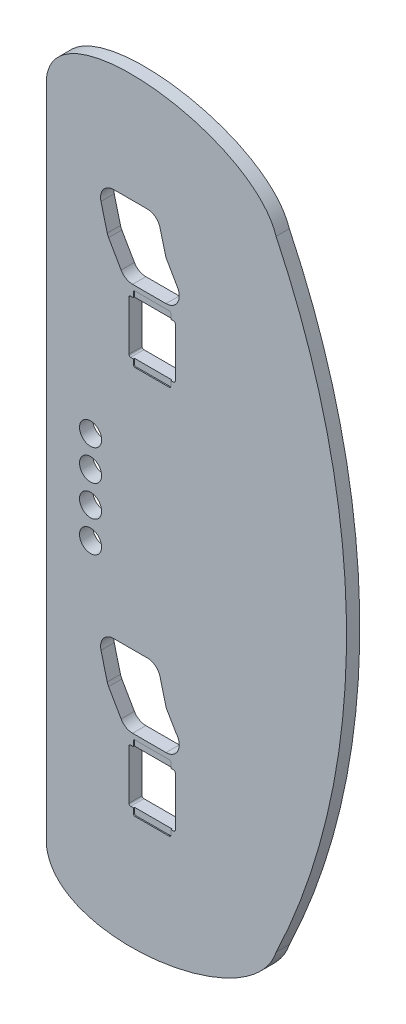
SolidWorks part; units mm, degrees
material "Pine"
ref_plane "Front Plane" through (0, 0, 0) normal (0, 0, 1) x (1, 0, 0)
ref_plane "Top Plane" through (0, 0, 0) normal (0, 1, 0) x (1, 0, 0)
ref_plane "Right Plane" through (0, 0, 0) normal (1, 0, 0) x (0, 0, -1)
sketch "Sketch1" plane through (0, 0, 0) normal (0, 1, 0) x (1, 0, 0)
  line L0 (-92.9216, 89.0184) -> (669.0784, 89.0184)
  line L1 (669.0784, 89.0184) -> (669.0784, 419.2184)
  line L2 (-92.9216, 89.0184) -> (-92.9216, 419.2184)
  line L5 (110.2784, 495.4184) -> (465.8784, 495.4184)
  line L8 (110.2784, 495.4184) -> (-92.9216, 419.2184)
  line L9 (465.8784, 495.4184) -> (669.0784, 419.2184)
  line L10 (-92.9216, 495.4184) -> (669.0784, 495.4184) construction
sketch "Sketch2" plane through (0, 0, 0) normal (0, 0, 1) x (1, 0, 0)
  line L95 (1361.0966, 1819.7347) -> (1361.0966, 996.3635)
  arc A0 (1691.2966, 1027.0491) -> (1691.2966, 1789.0491) centre (733.0004, 1408.0491) ccw
  spline S0 degree 3 poles (1691.2966, 1027.0491) (1656.7077, 922.0591) (1371.3251, 886.2968) (1361.0966, 996.3635) knots 0 0 0 0 7.629784 7.629784 7.629784 7.629784
  spline S1 degree 3 poles (1691.2966, 1789.0491) (1656.7629, 1894.0573) (1371.3251, 1929.8013) (1361.0966, 1819.7347) knots 0 0 0 0 7.638295 7.638295 7.638295 7.638295
sketch "Sketch4" plane through (0, 0, 0) normal (0, 0, 1) x (1, 0, 0)
  line L0 (1439.599, 1277.0692) -> (1448.5991, 1242.0693)
  line L1 (1450.5414, 1237.3053) -> (1468.5414, 1206.0553)
  line L2 (1540.0357, 1097.2035) -> (1540.0357, 1104.1885)
  line L3 (1486.0607, 1185.151) -> (1486.0607, 1006.8697) construction
  line L4 (1486.0607, 1187.3735) -> (1486.0607, 1180.3885)
  line L5 (1540.0357, 1006.8697) -> (1540.0357, 1185.151) construction
  line L6 (1544.7982, 1189.9135) -> (1481.2982, 1189.9135) construction
  line L7 (1488.6007, 1094.6635) -> (1537.4957, 1094.6635)
  line L8 (1482.2507, 1104.1885) -> (1543.8457, 1104.1885)
  line L9 (1546.3857, 1106.7285) -> (1546.3857, 1177.8485)
  line L10 (1543.8457, 1180.3885) -> (1482.2507, 1180.3885)
  line L11 (1479.7107, 1106.7285) -> (1479.7107, 1177.8485)
  line L12 (1540.0357, 1656.0035) -> (1540.0357, 1662.9885)
  line L13 (1488.6007, 1653.4635) -> (1537.4957, 1653.4635)
  line L14 (1543.8457, 1739.1885) -> (1482.2507, 1739.1885)
  line L15 (1486.0607, 1746.1735) -> (1486.0607, 1739.1885)
  line L16 (1479.7107, 1665.5285) -> (1479.7107, 1736.6485)
  line L17 (1537.4957, 1748.7135) -> (1488.6007, 1748.7135)
  line L18 (1482.2507, 1662.9885) -> (1543.8457, 1662.9885)
  line L19 (1546.3857, 1665.5285) -> (1546.3857, 1736.6485)
  line L20 (1540.0357, 1180.3885) -> (1540.0357, 1187.3735)
  line L21 (1486.0607, 1104.1885) -> (1486.0607, 1097.2035)
  line L22 (1540.0357, 1739.1885) -> (1540.0357, 1746.1735)
  line L23 (1486.0607, 1662.9885) -> (1486.0607, 1656.0035)
  line L24 (1485.0488, 1196.5135) -> (1533.0488, 1196.5135)
  line L25 (1550.8991, 1222.2168) -> (1533.383, 1252.007)
  line L26 (1524.4986, 1286.5577) -> (1533.383, 1252.007)
  line L27 (1459.748, 1300.7875) -> (1504.3496, 1300.7875)
  line L28 (1439.599, 1835.8692) -> (1448.5991, 1800.8693)
  line L29 (1450.5414, 1796.1053) -> (1468.5414, 1764.8553)
  line L30 (1485.0488, 1755.3135) -> (1533.0488, 1755.3135)
  line L31 (1549.5562, 1783.8718) -> (1532.852, 1812.8721)
  line L32 (1524.4986, 1845.3577) -> (1532.852, 1812.8721)
  line L33 (1458.0488, 1859.6635) -> (1506.0488, 1859.6635)
  line L34 (1513.0482, 1748.7135) -> (1513.0482, 1755.3135)
  line L38 (1513.0482, 1189.9135) -> (1513.0482, 1196.5135)
  line L95 (1361.0966, 1948.8635) -> (1361.0966, 996.3635)
  line L115 (1537.4957, 1189.9135) -> (1488.6007, 1189.9135)
  line L202 (1540.0357, 1185.151) -> (1486.0607, 1185.151) construction
  line L203 (1481.2982, 1189.9135) -> (1481.2982, 1006.8697) construction
  line L204 (1544.7982, 1006.8697) -> (1544.7982, 1189.9135) construction
  arc A0 (1691.2966, 1027.0491) -> (1691.2966, 1918.1779) centre (761.2616, 1472.6135) ccw
  arc A1 (1524.4986, 1286.5577) -> (1504.3496, 1300.7875) centre (1506.0488, 1281.8135) ccw
  arc A2 (1479.7107, 1177.8485) -> (1482.2507, 1180.3885) centre (1482.2507, 1177.8485) cw
  arc A3 (1533.0488, 1196.5135) -> (1547.5414, 1227.9274) centre (1533.0488, 1215.5635) ccw
  arc A4 (1448.5991, 1242.0693) -> (1450.5414, 1237.3053) centre (1467.0488, 1246.8135) ccw
  arc A5 (1468.5414, 1206.0553) -> (1485.0488, 1196.5135) centre (1485.0488, 1215.5635) ccw
  arc A6 (1459.748, 1300.7875) -> (1439.599, 1277.0692) centre (1458.0488, 1281.8135) ccw
  circle A7 centre (1513.0482, 1142.2885) radius 12
  arc A8 (1524.4986, 1845.3577) -> (1506.0488, 1859.6635) centre (1506.0488, 1840.6135) ccw
  arc A9 (1546.3857, 1177.8485) -> (1543.8457, 1180.3885) centre (1543.8457, 1177.8485) ccw
  arc A10 (1533.0488, 1755.3135) -> (1549.5562, 1783.8718) centre (1533.0488, 1774.3635) ccw
  arc A11 (1448.5991, 1800.8693) -> (1450.5414, 1796.1053) centre (1467.0488, 1805.6135) ccw
  arc A12 (1543.8457, 1104.1885) -> (1546.3857, 1106.7285) centre (1543.8457, 1106.7285) ccw
  arc A13 (1458.0488, 1859.6635) -> (1439.599, 1835.8692) centre (1458.0488, 1840.6135) ccw
  arc A14 (1482.2507, 1104.1885) -> (1479.7107, 1106.7285) centre (1482.2507, 1106.7285) cw
  arc A15 (1488.6007, 1094.6635) -> (1486.0607, 1097.2035) centre (1488.6007, 1097.2035) cw
  arc A16 (1537.4957, 1094.6635) -> (1540.0357, 1097.2035) centre (1537.4957, 1097.2035) ccw
  arc A17 (1479.7107, 1736.6485) -> (1482.2507, 1739.1885) centre (1482.2507, 1736.6485) cw
  arc A18 (1546.3857, 1736.6485) -> (1543.8457, 1739.1885) centre (1543.8457, 1736.6485) ccw
  circle A19 centre (1513.0482, 1701.0885) radius 12
  arc A20 (1468.5414, 1764.8553) -> (1485.0488, 1755.3135) centre (1485.0488, 1774.3635) ccw
  arc A21 (1540.0357, 1746.1735) -> (1537.4957, 1748.7135) centre (1537.4957, 1746.1735) ccw
  arc A22 (1486.0607, 1746.1735) -> (1488.6007, 1748.7135) centre (1488.6007, 1746.1735) cw
  arc A23 (1543.8457, 1662.9885) -> (1546.3857, 1665.5285) centre (1543.8457, 1665.5285) ccw
  arc A24 (1537.4957, 1653.4635) -> (1540.0357, 1656.0035) centre (1537.4957, 1656.0035) ccw
  arc A25 (1488.6007, 1653.4635) -> (1486.0607, 1656.0035) centre (1488.6007, 1656.0035) cw
  arc A26 (1479.7107, 1665.5285) -> (1482.2507, 1662.9885) centre (1482.2507, 1665.5285) ccw
  arc A27 (1540.0357, 1187.3735) -> (1537.4957, 1189.9135) centre (1537.4957, 1187.3735) ccw
  arc A28 (1486.0607, 1187.3735) -> (1488.6007, 1189.9135) centre (1488.6007, 1187.3735) cw
  circle A29 centre (1424.5966, 1539.2885) radius 15.875
  circle A30 centre (1424.5966, 1494.8385) radius 15.875
  circle A31 centre (1424.5966, 1450.3885) radius 15.875
  circle A32 centre (1424.5966, 1405.9385) radius 15.875
  spline S0 degree 3 poles (1691.2966, 1027.0491) (1656.7077, 922.0591) (1371.3251, 886.2968) (1361.0966, 996.3635) knots 0 0 0 0 7.629784 7.629784 7.629784 7.629784
  spline S1 degree 3 poles (1691.2966, 1918.1779) (1656.7629, 2023.1861) (1371.3251, 2058.9302) (1361.0966, 1948.8635) knots 0 0 0 0 7.638295 7.638295 7.638295 7.638295
  dimension "D2" = 2.54
  dimension "D4" = 2.54
  dimension "D5" = 2.54
  dimension "D6" = 2.54
  dimension "D7" = 2.54
  dimension "D8" = 2.54
  dimension "D9" = 2.54
  dimension "D3" = 2.54
  dimension "D15" = 2.54
  dimension "D1" = 4.7625
sketch "Sketch5" plane through (0, 0, 0) normal (0, 0, 1) x (1, 0, 0)
  line L0 (1361.0966, 1819.7347) -> (1361.0966, 996.3635)
  line L1 (1361.0966, 1789.0491) -> (1361.0966, 1027.0491)
  line L2 (1540.0357, 1006.8697) -> (1540.0357, 1016.3947)
  line L3 (1486.0607, 1097.3572) -> (1486.0607, 1006.8697) construction
  line L4 (1486.0607, 1102.1197) -> (1486.0607, 1092.5947)
  line L5 (1540.0357, 1006.8697) -> (1540.0357, 1097.3572) construction
  line L6 (1544.7982, 1102.1197) -> (1481.2982, 1102.1197) construction
  line L7 (1486.0607, 1006.8697) -> (1540.0357, 1006.8697)
  line L8 (1479.7107, 1016.3947) -> (1546.3857, 1016.3947)
  line L9 (1546.3857, 1016.3947) -> (1546.3857, 1092.5947)
  line L10 (1546.3857, 1092.5947) -> (1479.7107, 1092.5947)
  line L11 (1479.7107, 1016.3947) -> (1479.7107, 1092.5947)
  line L12 (1540.0357, 1548.8399) -> (1540.0357, 1558.3649)
  line L13 (1486.0607, 1548.8399) -> (1540.0357, 1548.8399)
  line L14 (1546.3857, 1634.5649) -> (1479.7107, 1634.5649)
  line L15 (1486.0607, 1644.0899) -> (1486.0607, 1634.5649)
  line L16 (1479.7107, 1558.3649) -> (1479.7107, 1634.5649)
  line L17 (1540.0357, 1644.0899) -> (1486.0607, 1644.0899)
  line L18 (1479.7107, 1558.3649) -> (1546.3857, 1558.3649)
  line L19 (1546.3857, 1558.3649) -> (1546.3857, 1634.5649)
  line L20 (1540.0357, 1092.5947) -> (1540.0357, 1102.1197)
  line L21 (1486.0607, 1016.3947) -> (1486.0607, 1006.8697)
  line L22 (1540.0357, 1634.5649) -> (1540.0357, 1644.0899)
  line L23 (1486.0607, 1558.3649) -> (1486.0607, 1548.8399)
  line L95 (1361.0966, 1819.7347) -> (1361.0966, 996.3635)
  line L115 (1540.0357, 1102.1197) -> (1486.0607, 1102.1197)
  line L199 (1363.2449, 1823.8418) -> (1361.0966, 1819.7347)
  line L200 (1361.0966, 1819.7347) -> (1361.7967, 1824.3165)
  line L201 (1361.7967, 1824.3165) -> (1363.2449, 1823.8418)
  line L202 (1540.0357, 1097.3572) -> (1486.0607, 1097.3572) construction
  line L203 (1481.2982, 1102.1197) -> (1481.2982, 1006.8697) construction
  line L204 (1544.7982, 1006.8697) -> (1544.7982, 1102.1197) construction
  arc A0 (1691.2966, 1027.0491) -> (1691.2966, 1789.0491) centre (733.0004, 1408.0491) ccw
  circle A1 centre (1506.0488, 1194.0197) radius 15.875
  circle A2 centre (1515.0488, 1159.0198) radius 15.875
  circle A3 centre (1533.0488, 1127.7698) radius 15.875
  circle A4 centre (1467.0488, 1159.0198) radius 15.875
  circle A5 centre (1485.0488, 1127.7698) radius 15.875
  circle A6 centre (1458.0488, 1194.0197) radius 15.875
  circle A7 centre (1513.0482, 1054.4947) radius 12
  circle A8 centre (1506.0488, 1735.9899) radius 15.875
  circle A9 centre (1515.0488, 1700.99) radius 15.875
  circle A10 centre (1533.0488, 1669.74) radius 15.875
  circle A11 centre (1467.0488, 1700.99) radius 15.875
  circle A12 centre (1485.0488, 1669.74) radius 15.875
  circle A13 centre (1458.0488, 1735.9899) radius 15.875
  circle A15 centre (1483.5084, 1375.1967) radius 12
  circle A16 centre (1483.9827, 1438.6917) radius 12
  circle A17 centre (1551.8392, 1408.0266) radius 29.9999
  circle A18 centre (1409.3368, 1408.0266) radius 15.9995
  circle A19 centre (1513.0482, 1596.4649) radius 12
  arc A30 (1539.4945, 1725.9331) -> (1482.0488, 1761.3623) centre (1506.0488, 1735.9899) ccw
  arc A32 (1549.9668, 1700.2938) -> (1539.4945, 1725.9331) centre (1515.0488, 1700.99) ccw
  arc A41 (1509.0488, 1644.3676) -> (1549.9668, 1700.2938) centre (1533.0488, 1669.74) ccw
  arc A46 (1450.1308, 1670.4362) -> (1509.0488, 1644.3676) centre (1485.0488, 1669.74) ccw
  arc A47 (1433.6031, 1711.0467) -> (1450.1308, 1670.4362) centre (1467.0488, 1700.99) ccw
  arc A50 (1482.0488, 1761.3623) -> (1433.6031, 1711.0467) centre (1458.0488, 1735.9899) ccw
  arc A64 (1509.0488, 1102.3974) -> (1549.9668, 1158.3235) centre (1533.0488, 1127.7698) ccw
  arc A66 (1450.1308, 1128.466) -> (1509.0488, 1102.3974) centre (1485.0488, 1127.7698) ccw
  arc A68 (1433.6031, 1169.0765) -> (1450.1308, 1128.466) centre (1467.0488, 1159.0198) ccw
  arc A70 (1539.4945, 1183.9629) -> (1482.0488, 1219.3921) centre (1506.0488, 1194.0197) ccw
  arc A72 (1549.9668, 1158.3235) -> (1539.4945, 1183.9629) centre (1515.0488, 1159.0198) ccw
  arc A73 (1482.0488, 1219.3921) -> (1433.6031, 1169.0765) centre (1458.0488, 1194.0197) ccw
  arc A86 (1474.249, 1382.8299) -> (1489.0021, 1364.5282) centre (1483.5084, 1375.1967) ccw
  arc A89 (1488.8753, 1449.649) -> (1474.6166, 1431.19) centre (1483.9827, 1438.6917) ccw
  arc A97 (1557.861, 1378.6372) -> (1557.0728, 1437.5665) centre (1551.8392, 1408.0266) ccw
  arc A99 (1420.1657, 1419.8299) -> (1400.5179, 1421.402) centre (1409.3362, 1408.0491) ccw
  arc A100 (1402.6554, 1393.5084) -> (1419.641, 1395.8067) centre (1409.3362, 1408.0491) ccw
  spline S0 degree 3 poles (1691.2966, 1027.0491) (1656.7077, 922.0591) (1371.3251, 886.2968) (1361.0966, 996.3635) knots 0 0 0 0 7.629784 7.629784 7.629784 7.629784
  spline S1 degree 3 poles (1691.2966, 1789.0491) (1656.7629, 1894.0573) (1371.3251, 1929.8013) (1361.0966, 1819.7347) knots 0 0 0 0 7.638295 7.638295 7.638295 7.638295
  dimension "D1" = 4.7625
extrude "Boss-Extrude6" add sketch "Sketch4" along normal blind 19.05 contours A0 S1 L95 S0 L33 L22 L14 L19 L18 L12 L13 L23 L16 L15 L20 L10 L9 L8 L2 L7 L21 L11 region at (1560.5051, 1471.6386, 0)
sketch "Sketch8" plane through (0, 0, 0) normal (0, 0, 1) x (1, 0, 0)
  line L2 (1540.0357, 1006.8697) -> (1540.0357, 1016.3947)
  line L3 (1486.0607, 1097.3572) -> (1486.0607, 1006.8697) construction
  line L4 (1486.0607, 1102.1197) -> (1486.0607, 1092.5947)
  line L5 (1540.0357, 1006.8697) -> (1540.0357, 1097.3572) construction
  line L6 (1544.7982, 1102.1197) -> (1481.2982, 1102.1197) construction
  line L7 (1486.0607, 1006.8697) -> (1540.0357, 1006.8697)
  line L8 (1479.7107, 1016.3947) -> (1546.3857, 1016.3947)
  line L9 (1546.3857, 1016.3947) -> (1546.3857, 1092.5947)
  line L10 (1546.3857, 1092.5947) -> (1479.7107, 1092.5947)
  line L11 (1479.7107, 1016.3947) -> (1479.7107, 1092.5947)
  line L12 (1540.0357, 1548.8399) -> (1540.0357, 1558.3649)
  line L13 (1486.0607, 1548.8399) -> (1540.0357, 1548.8399)
  line L14 (1546.3857, 1634.5649) -> (1479.7107, 1634.5649)
  line L15 (1486.0607, 1644.0899) -> (1486.0607, 1634.5649)
  line L16 (1479.7107, 1558.3649) -> (1479.7107, 1634.5649)
  line L17 (1540.0357, 1644.0899) -> (1486.0607, 1644.0899)
  line L18 (1479.7107, 1558.3649) -> (1546.3857, 1558.3649)
  line L19 (1546.3857, 1558.3649) -> (1546.3857, 1634.5649)
  line L20 (1540.0357, 1092.5947) -> (1540.0357, 1102.1197)
  line L21 (1486.0607, 1016.3947) -> (1486.0607, 1006.8697)
  line L22 (1540.0357, 1634.5649) -> (1540.0357, 1644.0899)
  line L23 (1486.0607, 1558.3649) -> (1486.0607, 1548.8399)
  line L95 (1361.0966, 1819.7347) -> (1361.0966, 996.3635)
  line L115 (1540.0357, 1102.1197) -> (1486.0607, 1102.1197)
  line L202 (1540.0357, 1097.3572) -> (1486.0607, 1097.3572) construction
  line L203 (1481.2982, 1102.1197) -> (1481.2982, 1006.8697) construction
  line L204 (1544.7982, 1006.8697) -> (1544.7982, 1102.1197) construction
  arc A0 (1691.2966, 1027.0491) -> (1691.2966, 1789.0491) centre (733.0004, 1408.0491) ccw
  circle A1 centre (1506.0488, 1194.0197) radius 15.875
  circle A2 centre (1515.0488, 1159.0198) radius 15.875
  circle A3 centre (1533.0488, 1127.7698) radius 15.875
  circle A4 centre (1467.0488, 1159.0198) radius 15.875
  circle A5 centre (1485.0488, 1127.7698) radius 15.875
  circle A6 centre (1458.0488, 1194.0197) radius 15.875
  circle A7 centre (1513.0482, 1054.4947) radius 12
  circle A8 centre (1506.0488, 1735.9899) radius 15.875
  circle A9 centre (1515.0488, 1700.99) radius 15.875
  circle A10 centre (1533.0488, 1669.74) radius 15.875
  circle A11 centre (1467.0488, 1700.99) radius 15.875
  circle A12 centre (1485.0488, 1669.74) radius 15.875
  circle A13 centre (1458.0488, 1735.9899) radius 15.875
  circle A15 centre (1483.5084, 1375.1967) radius 12
  circle A16 centre (1483.9827, 1438.6917) radius 12
  circle A17 centre (1551.8392, 1408.0266) radius 29.9999
  circle A18 centre (1409.3368, 1408.0266) radius 15.9995
  circle A19 centre (1513.0482, 1596.4649) radius 12
  arc A30 (1539.4945, 1725.9331) -> (1482.0488, 1761.3623) centre (1506.0488, 1735.9899) ccw
  arc A32 (1549.9668, 1700.2938) -> (1539.4945, 1725.9331) centre (1515.0488, 1700.99) ccw
  arc A41 (1509.0488, 1644.3676) -> (1549.9668, 1700.2938) centre (1533.0488, 1669.74) ccw
  arc A46 (1450.1308, 1670.4362) -> (1509.0488, 1644.3676) centre (1485.0488, 1669.74) ccw
  arc A47 (1433.6031, 1711.0467) -> (1450.1308, 1670.4362) centre (1467.0488, 1700.99) ccw
  arc A50 (1482.0488, 1761.3623) -> (1433.6031, 1711.0467) centre (1458.0488, 1735.9899) ccw
  arc A64 (1509.0488, 1102.3974) -> (1549.9668, 1158.3235) centre (1533.0488, 1127.7698) ccw
  arc A66 (1450.1308, 1128.466) -> (1509.0488, 1102.3974) centre (1485.0488, 1127.7698) ccw
  arc A68 (1433.6031, 1169.0765) -> (1450.1308, 1128.466) centre (1467.0488, 1159.0198) ccw
  arc A70 (1539.4945, 1183.9629) -> (1482.0488, 1219.3921) centre (1506.0488, 1194.0197) ccw
  arc A72 (1549.9668, 1158.3235) -> (1539.4945, 1183.9629) centre (1515.0488, 1159.0198) ccw
  arc A73 (1482.0488, 1219.3921) -> (1433.6031, 1169.0765) centre (1458.0488, 1194.0197) ccw
  arc A86 (1474.249, 1382.8299) -> (1489.0021, 1364.5282) centre (1483.5084, 1375.1967) ccw
  arc A89 (1488.8753, 1449.649) -> (1474.6166, 1431.19) centre (1483.9827, 1438.6917) ccw
  arc A97 (1557.861, 1378.6372) -> (1557.0728, 1437.5665) centre (1551.8392, 1408.0266) ccw
  arc A99 (1420.1657, 1419.8299) -> (1400.5179, 1421.402) centre (1409.3362, 1408.0491) ccw
  arc A100 (1402.6554, 1393.5084) -> (1419.641, 1395.8067) centre (1409.3362, 1408.0491) ccw
  spline S0 degree 3 poles (1691.2966, 1027.0491) (1656.7077, 922.0591) (1371.3251, 886.2968) (1361.0966, 996.3635) knots 0 0 0 0 7.629784 7.629784 7.629784 7.629784
  spline S1 degree 3 poles (1691.2966, 1789.0491) (1656.7629, 1894.0573) (1371.3251, 1929.8013) (1361.0966, 1819.7347) knots 0 0 0 0 7.638295 7.638295 7.638295 7.638295
  dimension "D1" = 4.7625
sketch "Sketch9" plane through (0, 0, 0) normal (0, 0, 1) x (1, 0, 0)
  line L2 (1540.0357, 1006.8697) -> (1540.0357, 1016.3947)
  line L3 (1486.0607, 1097.3572) -> (1486.0607, 1006.8697) construction
  line L4 (1486.0607, 1102.1197) -> (1486.0607, 1092.5947)
  line L5 (1540.0357, 1006.8697) -> (1540.0357, 1097.3572) construction
  line L6 (1544.7982, 1102.1197) -> (1481.2982, 1102.1197) construction
  line L7 (1486.0607, 1006.8697) -> (1540.0357, 1006.8697)
  line L8 (1479.7107, 1016.3947) -> (1546.3857, 1016.3947)
  line L9 (1546.3857, 1016.3947) -> (1546.3857, 1092.5947)
  line L10 (1546.3857, 1092.5947) -> (1479.7107, 1092.5947)
  line L11 (1479.7107, 1016.3947) -> (1479.7107, 1092.5947)
  line L12 (1540.0357, 1548.8399) -> (1540.0357, 1558.3649)
  line L13 (1486.0607, 1548.8399) -> (1540.0357, 1548.8399)
  line L14 (1546.3857, 1634.5649) -> (1479.7107, 1634.5649)
  line L15 (1486.0607, 1644.0899) -> (1486.0607, 1634.5649)
  line L16 (1479.7107, 1558.3649) -> (1479.7107, 1634.5649)
  line L17 (1540.0357, 1644.0899) -> (1486.0607, 1644.0899)
  line L18 (1479.7107, 1558.3649) -> (1546.3857, 1558.3649)
  line L19 (1546.3857, 1558.3649) -> (1546.3857, 1634.5649)
  line L20 (1540.0357, 1092.5947) -> (1540.0357, 1102.1197)
  line L21 (1486.0607, 1016.3947) -> (1486.0607, 1006.8697)
  line L22 (1540.0357, 1634.5649) -> (1540.0357, 1644.0899)
  line L23 (1486.0607, 1558.3649) -> (1486.0607, 1548.8399)
  line L95 (1361.0966, 1819.7347) -> (1361.0966, 996.3635)
  line L115 (1540.0357, 1102.1197) -> (1486.0607, 1102.1197)
  line L202 (1540.0357, 1097.3572) -> (1486.0607, 1097.3572) construction
  line L203 (1481.2982, 1102.1197) -> (1481.2982, 1006.8697) construction
  line L204 (1544.7982, 1006.8697) -> (1544.7982, 1102.1197) construction
  arc A0 (1691.2966, 1027.0491) -> (1691.2966, 1789.0491) centre (733.0004, 1408.0491) ccw
  circle A1 centre (1506.0488, 1194.0197) radius 15.875
  circle A2 centre (1515.0488, 1159.0198) radius 15.875
  circle A3 centre (1533.0488, 1127.7698) radius 15.875
  circle A4 centre (1467.0488, 1159.0198) radius 15.875
  circle A5 centre (1485.0488, 1127.7698) radius 15.875
  circle A6 centre (1458.0488, 1194.0197) radius 15.875
  circle A7 centre (1513.0482, 1054.4947) radius 12
  circle A8 centre (1506.0488, 1735.9899) radius 15.875
  circle A9 centre (1515.0488, 1700.99) radius 15.875
  circle A10 centre (1533.0488, 1669.74) radius 15.875
  circle A11 centre (1467.0488, 1700.99) radius 15.875
  circle A12 centre (1485.0488, 1669.74) radius 15.875
  circle A13 centre (1458.0488, 1735.9899) radius 15.875
  circle A15 centre (1483.5084, 1375.1967) radius 12
  circle A16 centre (1483.9827, 1438.6917) radius 12
  circle A17 centre (1551.8392, 1408.0266) radius 29.9999
  circle A18 centre (1409.3368, 1408.0266) radius 15.9995
  circle A19 centre (1513.0482, 1596.4649) radius 12
  arc A30 (1539.4945, 1725.9331) -> (1482.0488, 1761.3623) centre (1506.0488, 1735.9899) ccw
  arc A32 (1549.9668, 1700.2938) -> (1539.4945, 1725.9331) centre (1515.0488, 1700.99) ccw
  arc A41 (1509.0488, 1644.3676) -> (1549.9668, 1700.2938) centre (1533.0488, 1669.74) ccw
  arc A46 (1450.1308, 1670.4362) -> (1509.0488, 1644.3676) centre (1485.0488, 1669.74) ccw
  arc A47 (1433.6031, 1711.0467) -> (1450.1308, 1670.4362) centre (1467.0488, 1700.99) ccw
  arc A50 (1482.0488, 1761.3623) -> (1433.6031, 1711.0467) centre (1458.0488, 1735.9899) ccw
  arc A64 (1509.0488, 1102.3974) -> (1549.9668, 1158.3235) centre (1533.0488, 1127.7698) ccw
  arc A66 (1450.1308, 1128.466) -> (1509.0488, 1102.3974) centre (1485.0488, 1127.7698) ccw
  arc A68 (1433.6031, 1169.0765) -> (1450.1308, 1128.466) centre (1467.0488, 1159.0198) ccw
  arc A70 (1539.4945, 1183.9629) -> (1482.0488, 1219.3921) centre (1506.0488, 1194.0197) ccw
  arc A72 (1549.9668, 1158.3235) -> (1539.4945, 1183.9629) centre (1515.0488, 1159.0198) ccw
  arc A73 (1482.0488, 1219.3921) -> (1433.6031, 1169.0765) centre (1458.0488, 1194.0197) ccw
  arc A86 (1474.249, 1382.8299) -> (1489.0021, 1364.5282) centre (1483.5084, 1375.1967) ccw
  arc A89 (1488.8753, 1449.649) -> (1474.6166, 1431.19) centre (1483.9827, 1438.6917) ccw
  arc A97 (1557.861, 1378.6372) -> (1557.0728, 1437.5665) centre (1551.8392, 1408.0266) ccw
  arc A99 (1420.1657, 1419.8299) -> (1400.5179, 1421.402) centre (1409.3362, 1408.0491) ccw
  arc A100 (1402.6554, 1393.5084) -> (1419.641, 1395.8067) centre (1409.3362, 1408.0491) ccw
  spline S0 degree 3 poles (1691.2966, 1027.0491) (1656.7077, 922.0591) (1371.3251, 886.2968) (1361.0966, 996.3635) knots 0 0 0 0 7.629784 7.629784 7.629784 7.629784
  spline S1 degree 3 poles (1691.2966, 1789.0491) (1656.7629, 1894.0573) (1371.3251, 1929.8013) (1361.0966, 1819.7347) knots 0 0 0 0 7.638295 7.638295 7.638295 7.638295
  dimension "D1" = 4.7625
sketch "Sketch13" plane through (0, 0, 0) normal (0, 0, 1) x (1, 0, 0)
  line L0 (1439.599, 1277.0692) -> (1448.5991, 1242.0693)
  line L1 (1450.5414, 1237.3053) -> (1468.5414, 1206.0553)
  line L2 (1540.0357, 1097.2035) -> (1540.0357, 1104.1885)
  line L3 (1486.0607, 1185.151) -> (1486.0607, 1006.8697) construction
  line L4 (1486.0607, 1187.3735) -> (1486.0607, 1180.3885)
  line L5 (1540.0357, 1006.8697) -> (1540.0357, 1185.151) construction
  line L6 (1544.7982, 1189.9135) -> (1481.2982, 1189.9135) construction
  line L7 (1488.6007, 1094.6635) -> (1537.4957, 1094.6635)
  line L8 (1482.2507, 1104.1885) -> (1543.8457, 1104.1885)
  line L9 (1546.3857, 1106.7285) -> (1546.3857, 1177.8485)
  line L10 (1543.8457, 1180.3885) -> (1482.2507, 1180.3885)
  line L11 (1479.7107, 1106.7285) -> (1479.7107, 1177.8485)
  line L12 (1540.0357, 1656.0035) -> (1540.0357, 1662.9885)
  line L13 (1488.6007, 1653.4635) -> (1537.4957, 1653.4635)
  line L14 (1543.8457, 1739.1885) -> (1482.2507, 1739.1885)
  line L15 (1486.0607, 1746.1735) -> (1486.0607, 1739.1885)
  line L16 (1479.7107, 1665.5285) -> (1479.7107, 1736.6485)
  line L17 (1537.4957, 1748.7135) -> (1488.6007, 1748.7135)
  line L18 (1482.2507, 1662.9885) -> (1543.8457, 1662.9885)
  line L19 (1546.3857, 1665.5285) -> (1546.3857, 1736.6485)
  line L20 (1540.0357, 1180.3885) -> (1540.0357, 1187.3735)
  line L21 (1486.0607, 1104.1885) -> (1486.0607, 1097.2035)
  line L22 (1540.0357, 1739.1885) -> (1540.0357, 1746.1735)
  line L23 (1486.0607, 1662.9885) -> (1486.0607, 1656.0035)
  line L24 (1485.0488, 1196.5135) -> (1533.0488, 1196.5135)
  line L25 (1550.8991, 1222.2168) -> (1533.383, 1252.007)
  line L26 (1524.4986, 1286.5577) -> (1533.383, 1252.007)
  line L27 (1459.748, 1300.7875) -> (1504.3496, 1300.7875)
  line L28 (1439.599, 1835.8692) -> (1448.5991, 1800.8693)
  line L29 (1450.5414, 1796.1053) -> (1468.5414, 1764.8553)
  line L30 (1485.0488, 1755.3135) -> (1533.0488, 1755.3135)
  line L31 (1549.5562, 1783.8718) -> (1532.852, 1812.8721)
  line L32 (1524.4986, 1845.3577) -> (1532.852, 1812.8721)
  line L33 (1458.0488, 1859.6635) -> (1506.0488, 1859.6635)
  line L34 (1513.0482, 1748.7135) -> (1513.0482, 1755.3135)
  line L38 (1513.0482, 1189.9135) -> (1513.0482, 1196.5135)
  line L95 (1361.0966, 1948.8635) -> (1361.0966, 996.3635)
  line L115 (1537.4957, 1189.9135) -> (1488.6007, 1189.9135)
  line L202 (1540.0357, 1185.151) -> (1486.0607, 1185.151) construction
  line L203 (1481.2982, 1189.9135) -> (1481.2982, 1006.8697) construction
  line L204 (1544.7982, 1006.8697) -> (1544.7982, 1189.9135) construction
  arc A0 (1691.2966, 1027.0491) -> (1691.2966, 1918.1779) centre (761.2616, 1472.6135) ccw
  arc A1 (1524.4986, 1286.5577) -> (1504.3496, 1300.7875) centre (1506.0488, 1281.8135) ccw
  arc A2 (1479.7107, 1177.8485) -> (1482.2507, 1180.3885) centre (1482.2507, 1177.8485) cw
  arc A3 (1533.0488, 1196.5135) -> (1547.5414, 1227.9274) centre (1533.0488, 1215.5635) ccw
  arc A4 (1448.5991, 1242.0693) -> (1450.5414, 1237.3053) centre (1467.0488, 1246.8135) ccw
  arc A5 (1468.5414, 1206.0553) -> (1485.0488, 1196.5135) centre (1485.0488, 1215.5635) ccw
  arc A6 (1459.748, 1300.7875) -> (1439.599, 1277.0692) centre (1458.0488, 1281.8135) ccw
  circle A7 centre (1513.0482, 1142.2885) radius 12
  arc A8 (1524.4986, 1845.3577) -> (1506.0488, 1859.6635) centre (1506.0488, 1840.6135) ccw
  arc A9 (1546.3857, 1177.8485) -> (1543.8457, 1180.3885) centre (1543.8457, 1177.8485) ccw
  arc A10 (1533.0488, 1755.3135) -> (1549.5562, 1783.8718) centre (1533.0488, 1774.3635) ccw
  arc A11 (1448.5991, 1800.8693) -> (1450.5414, 1796.1053) centre (1467.0488, 1805.6135) ccw
  arc A12 (1543.8457, 1104.1885) -> (1546.3857, 1106.7285) centre (1543.8457, 1106.7285) ccw
  arc A13 (1458.0488, 1859.6635) -> (1439.599, 1835.8692) centre (1458.0488, 1840.6135) ccw
  arc A14 (1482.2507, 1104.1885) -> (1479.7107, 1106.7285) centre (1482.2507, 1106.7285) cw
  arc A15 (1488.6007, 1094.6635) -> (1486.0607, 1097.2035) centre (1488.6007, 1097.2035) cw
  arc A16 (1537.4957, 1094.6635) -> (1540.0357, 1097.2035) centre (1537.4957, 1097.2035) ccw
  arc A17 (1479.7107, 1736.6485) -> (1482.2507, 1739.1885) centre (1482.2507, 1736.6485) cw
  arc A18 (1546.3857, 1736.6485) -> (1543.8457, 1739.1885) centre (1543.8457, 1736.6485) ccw
  circle A19 centre (1513.0482, 1701.0885) radius 12
  arc A20 (1468.5414, 1764.8553) -> (1485.0488, 1755.3135) centre (1485.0488, 1774.3635) ccw
  arc A21 (1540.0357, 1746.1735) -> (1537.4957, 1748.7135) centre (1537.4957, 1746.1735) ccw
  arc A22 (1486.0607, 1746.1735) -> (1488.6007, 1748.7135) centre (1488.6007, 1746.1735) cw
  arc A23 (1543.8457, 1662.9885) -> (1546.3857, 1665.5285) centre (1543.8457, 1665.5285) ccw
  arc A24 (1537.4957, 1653.4635) -> (1540.0357, 1656.0035) centre (1537.4957, 1656.0035) ccw
  arc A25 (1488.6007, 1653.4635) -> (1486.0607, 1656.0035) centre (1488.6007, 1656.0035) cw
  arc A26 (1479.7107, 1665.5285) -> (1482.2507, 1662.9885) centre (1482.2507, 1665.5285) ccw
  arc A27 (1540.0357, 1187.3735) -> (1537.4957, 1189.9135) centre (1537.4957, 1187.3735) ccw
  arc A28 (1486.0607, 1187.3735) -> (1488.6007, 1189.9135) centre (1488.6007, 1187.3735) cw
  circle A29 centre (1424.5966, 1539.2885) radius 15.875
  circle A30 centre (1424.5966, 1494.8385) radius 15.875
  circle A31 centre (1424.5966, 1450.3885) radius 15.875
  circle A32 centre (1424.5966, 1405.9385) radius 15.875
  spline S0 degree 3 poles (1691.2966, 1027.0491) (1656.7077, 922.0591) (1371.3251, 886.2968) (1361.0966, 996.3635) knots 0 0 0 0 7.629784 7.629784 7.629784 7.629784
  spline S1 degree 3 poles (1691.2966, 1918.1779) (1656.7629, 2023.1861) (1371.3251, 2058.9302) (1361.0966, 1948.8635) knots 0 0 0 0 7.638295 7.638295 7.638295 7.638295
  dimension "D2" = 2.54
  dimension "D4" = 2.54
  dimension "D5" = 2.54
  dimension "D6" = 2.54
  dimension "D7" = 2.54
  dimension "D8" = 2.54
  dimension "D9" = 2.54
  dimension "D3" = 2.54
  dimension "D15" = 2.54
  dimension "D1" = 4.7625
extrude "Boss-Extrude7" add sketch "Sketch13" along normal blind 17.4625 contours A22 L15 L14 L22 A21 L17 | A25 L13 A24 L12 L18 L23 | A28 L4 L10 L20 A27 L115 | L7 A16 L2 L8 L21 A15 region at (1513.0482, 1185.1282, 0) region at (1513.0482, 1099.4487, 0) region at (1513.0482, 1658.2487, 0) region at (1513.0482, 1743.9282, 0)
